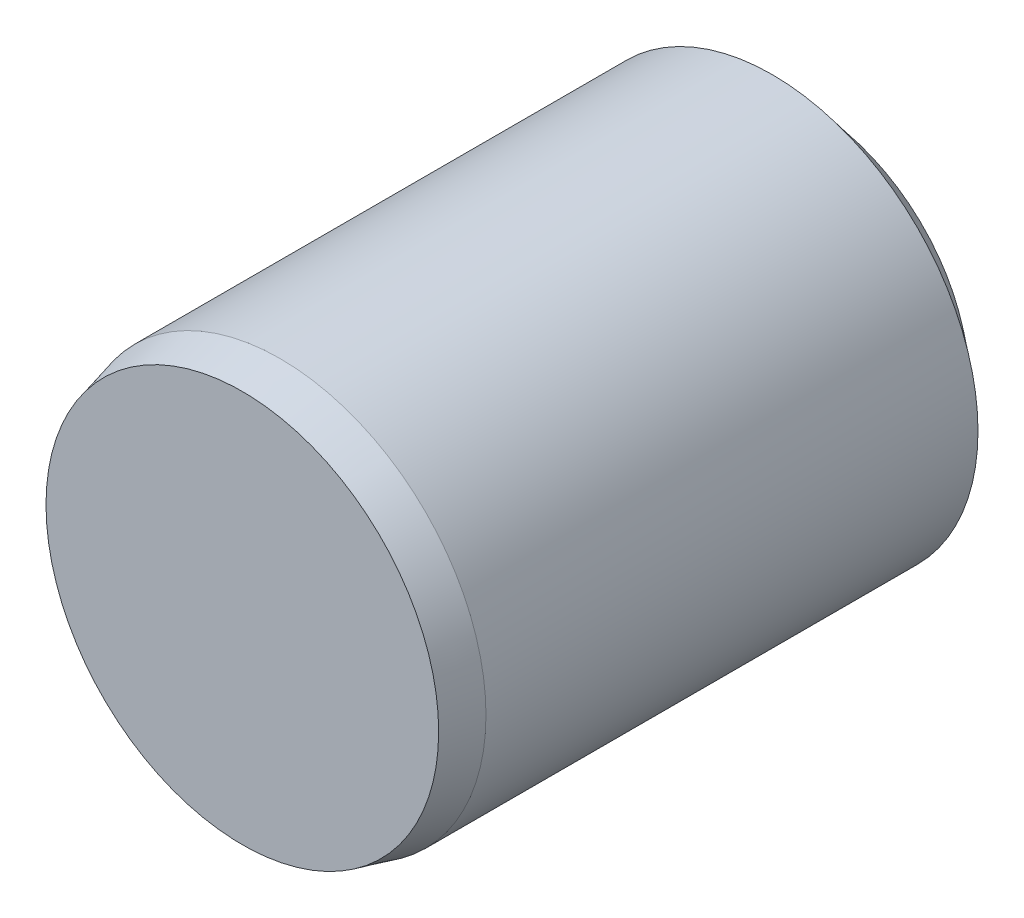
SolidWorks part; units mm, degrees
ref_plane "Front Plane" through (0, 0, 0) normal (0, 0, 1) x (1, 0, 0)
ref_plane "Top Plane" through (0, 0, 0) normal (0, 1, 0) x (1, 0, 0)
ref_plane "Right Plane" through (0, 0, 0) normal (1, 0, 0) x (0, 0, -1)
sketch "Sketch1" plane through (0, 0, 0) normal (1, 0, 0) x (0, 0, -1)
  line L0 (0, 53.34) -> (0, -53.34) construction
  line L1 (-12.7, 69.0563) -> (-12.7, -69.0563) construction
  line L2 (-177.8, 69.0563) -> (-177.8, -69.0563) construction
  line L3 (-190.5, 65.8813) -> (-190.5, -65.8813) construction
  line L4 (-190.5, 65.8813) -> (-177.8, 69.0563)
  line L5 (-177.8, 69.0563) -> (-12.7, 69.0563)
  line L6 (-12.7, 69.0563) -> (0, 53.34)
  line L7 (0, 53.34) -> (0, 47.7669)
  line L8 (0, 47.7669) -> (-12.7, 50.0063)
  line L9 (-12.7, 50.0063) -> (-115.0938, 50.0062)
  line L10 (-394.5694, 0) -> (118.2083, 0) construction
  line L11 (-165.1, 0) -> (-190.5, 0)
  line L12 (-190.5, 0) -> (-190.5, 65.8813)
  arc A0 (-115.0938, 50.0062) -> (-165.1, 0) centre (-115.0938, 0) ccw
  point P3 (-12.7, 0)
  point P4 (0, 0)
  point P11 (-177.8, 0)
  point P12 (-190.5, 0)
  point P20 (0, 47.039)
  dimension "D1" = 106.68
  dimension "D2" = 138.1125
  dimension "D3" = 12.7
  dimension "D4" = 12.7
  dimension "D5" = 131.7625
  dimension "D6" = 165.1
  dimension "D7" = 12.7
  dimension "D8" = 19.05
  dimension "D9" = 170
revolve "Revolve1" add sketch "Sketch1" angle 360 about L10
sketch "Sketch3" plane through (0, 0, 0) normal (1, 0, 0) x (0, 0, -1)
  line L0 (-86.7725, 50.0062) -> (-69.0101, -50.0062) construction
  line L1 (-12.7, 50.0062) -> (-115.0938, 50.0062) construction
  line L2 (-115.0938, -50.0062) -> (-12.7, -50.0062) construction
  line L3 (-69.0101, -50.0062) -> (-50.6422, -50.0062) construction
  line L4 (-50.6422, -50.0062) -> (-68.4046, 50.0062) construction
  line L5 (-68.4046, 50.0062) -> (-86.7725, 50.0062) construction
  line L6 (-77.5885, 50.0062) -> (-59.8262, -50.0062)
sketch "Sketch4" plane through (0, 0, 0) normal (0, 1, 0) x (1, 0, 0)
  line L0 (0, -69.0101) -> (0, -50.6422) construction
  circle A0 centre (0, -59.8262) radius 15.24
  dimension "D1" = 30.48
sweep "Sweep1" add profiles "Sketch4" path "Sketch3"
equation "\"D1@Sketch1\"=4+1/5"
equation "\"D2@Sketch1\"=5+7/16"
